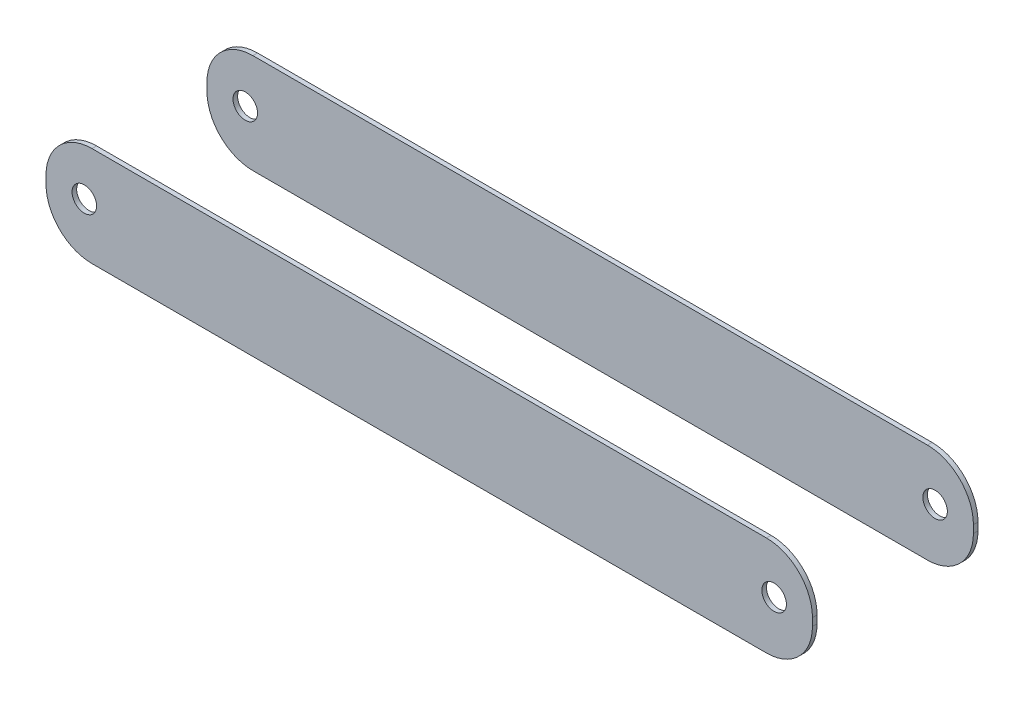
SolidWorks part; units mm, degrees
ref_plane "Front Plane" through (0, 0, 0) normal (0, 0, 1) x (1, 0, 0)
ref_plane "Top Plane" through (0, 0, 0) normal (0, 1, 0) x (1, 0, 0)
ref_plane "Right Plane" through (0, 0, 0) normal (1, 0, 0) x (0, 0, -1)
sketch "Sketch1" plane through (0, 0, 0) normal (0, 1, 0) x (1, 0, 0)
  line L1 (-233.8195, 144.485) -> (266.1805, 144.485)
  line L2 (-233.8195, 144.485) -> (-233.8195, 36.485)
  line L3 (-233.8195, 36.485) -> (266.1805, 36.485)
  line L4 (266.1805, 144.485) -> (266.1805, 36.485)
  line L5 (-233.8195, 141.485) -> (266.1805, 141.485)
  line L6 (-233.8195, 141.485) -> (-233.8195, 39.485)
  line L7 (-233.8195, 39.485) -> (266.1805, 39.485)
  line L8 (266.1805, 141.485) -> (266.1805, 39.485)
  dimension "D1" = 500
  dimension "D2" = 108
  dimension "D3" = 3
  dimension "D4" = 3
extrude "Boss-Extrude1" add sketch "Sketch1" along normal blind 65 contours L3 L4 L1 L2
sketch "Sketch3" plane through (0, 0, 0) normal (0, -1, 0) x (1, 0, 0)
  line L0 (-233.8195, -144.485) -> (-233.8195, -36.485) construction
  line L1 (-233.8195, -39.485) -> (266.1805, -39.485)
  line L2 (-233.8195, -39.485) -> (-233.8195, -141.485)
  line L3 (-233.8195, -141.485) -> (266.1805, -141.485)
  line L4 (266.1805, -39.485) -> (266.1805, -141.485)
  line L5 (266.1805, -144.485) -> (266.1805, -36.485) construction
  line L6 (-233.8195, -36.485) -> (266.1805, -36.485) construction
  line L7 (-233.8195, -144.485) -> (266.1805, -144.485) construction
  dimension "D1" = 3
  dimension "D2" = 3
extrude "Cut-Extrude1" cut sketch "Sketch3" against normal blind 158
sketch "Sketch4" plane through (0, 0, -36.485) normal (0, 0, 1) x (1, 0, 0)
  line L0 (-233.8195, 65) -> (266.1805, 65) construction
  line L1 (-233.8195, 65) -> (-233.8195, 0) construction
  line L2 (266.1805, 65) -> (266.1805, 0) construction
  circle A0 centre (-208.8195, 34) radius 8
  circle A1 centre (241.1805, 34) radius 8
  dimension "D1" = 16
  dimension "D2" = 31
  dimension "D3" = 25
  dimension "D4" = 25
  dimension "D5" = 16
  dimension "D6" = 31
extrude "Cut-Extrude2" cut sketch "Sketch4" against normal blind 158
fillet "Fillet1" radius 30 4 edges at (-233.8195, 65, -142.985) (-233.8195, 0, -142.985) (266.1805, 0, -142.985) (266.1805, 65, -142.985)
fillet "Fillet3" radius 30 4 edges at (266.1805, 0, -37.985) (266.1805, 65, -37.985) (-233.8195, 0, -37.985) (-233.8195, 65, -37.985)
